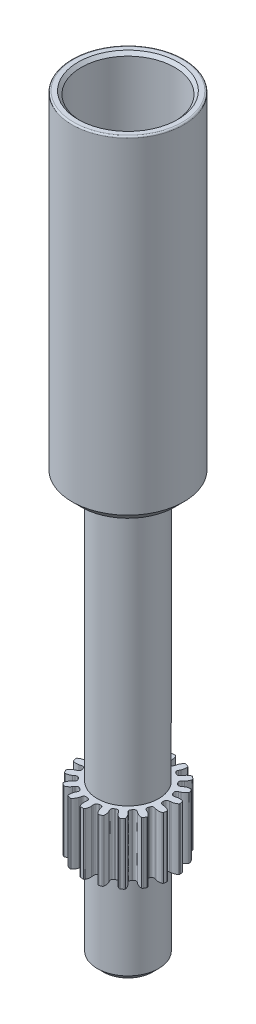
SolidWorks part; units mm, degrees
ref_plane "Front Plane" through (0, 0, 0) normal (0, 0, 1) x (1, 0, 0)
ref_plane "Top Plane" through (0, 0, 0) normal (0, 1, 0) x (1, 0, 0)
ref_plane "Right Plane" through (0, 0, 0) normal (1, 0, 0) x (0, 0, -1)
sketch "Sketch1" plane through (0, 0, 0) normal (0, 0, 1) x (1, 0, 0)
  line L0 (0, 0) -> (-10, 0)
  line L1 (-10, 0) -> (-10, 135)
  line L2 (-10, 135) -> (-18.25, 135)
  line L3 (-18.25, 135) -> (-18.25, 245)
  line L4 (-18.25, 245) -> (-15.25, 245)
  line L5 (-15.25, 245) -> (-15.25, 155)
  line L6 (-15.25, 155) -> (0, 155)
  line L7 (0, 155) -> (0, 0)
  line L8 (-7.3324, 35) -> (8.884, 35) construction
  dimension "D1" = 110
  dimension "D2" = 135
  dimension "D4" = 15.25
  dimension "D5" = 10
  dimension "D6" = 90
  dimension "D7" = 3
revolve "Revolve1" add sketch "Sketch1" angle 360 about L7
chamfer "Chamfer1" distance 3 angle 45 1 edges at (-18.25, 135, 0)
fillet "Fillet1" radius 0.5 1 edges at (-18.25, 245, 0)
ref_axis "Axis1" through (0, 155, 0) along (0, 1, 0)
chamfer "Chamfer2" distance 1 angle 45 1 edges at (-15.25, 245, 0)
ref_plane "Plane1" through (0, 30, 0) normal (0, -1, 0) x (-1, 0, 0)
sketch "Sketch2" plane through (0, 30, 0) normal (0, -1, 0) x (-1, 0, 0)
  line L0 (0, 0) -> (0, 50.5669) construction
  line L1 (0, 0) -> (-2.3642, 54.1494) construction
  line L2 (0, 0) -> (-4.5793, 52.3414) construction
  line L3 (0, 0) -> (-8.4968, 48.1875) construction
  line L16 (-1.133, 12.9505) -> (-1.0023, 11.4562)
  line L17 (-1.997, 11.3253) -> (0, 0)
  line L18 (1.997, 11.3253) -> (0, 0)
  line L19 (1.133, 12.9505) -> (1.0023, 11.4562)
  arc A0 (0.4277, 14.9939) -> (-0.4277, 14.9939) centre (0, 0) ccw
  circle A1 centre (0, 0) radius 13
  arc A2 (0.7715, 14.778) -> (1.133, 12.9505) centre (-2.1947, 13.2417) cw
  circle A3 centre (0, 0) radius 11.5
  arc A6 (-0.7715, 14.778) -> (-1.133, 12.9505) centre (2.1947, 13.2417) ccw
  arc A7 (-1.3073, 14.9429) -> (6.9708, 13.2818) centre (0, 0) ccw
  arc A8 (-0.7715, 14.778) -> (-0.4277, 14.9939) centre (-0.4163, 14.5941) cw
  arc A9 (0.7715, 14.778) -> (0.4277, 14.9939) centre (0.4163, 14.5941) ccw
  point P25 (0, 0)
  point P36 (-0.6543, 14.9857)
  point P39 (0.6543, 14.9857)
  dimension "D1" = 30
  dimension "D2" = 26
  dimension "D3" = 23
  dimension "D5" = 2.5
  dimension "D8" = 0.4
  dimension "D6" = 5
  dimension "D7" = 10
extrude "Boss-Extrude1" add sketch "Sketch2" against normal blind 20 contours A3 L17 L18 | A3 L19 A1 L16 | A0 A6 A1 A2 region at (0, 30, -12.2497) region at (0, 30, -13.9056) region at (0, 30, -7.6278)
fillet "Fillet2" radius 1 2 edges at (1.0023, 40, -11.4562) (-1.0023, 40, -11.4562) curvature continuous yes
pattern_circular "CirPattern2" count 18 over 360 about axis through (0, 155, 0) along (0, 1, 0) of "Fillet2", "Boss-Extrude1"
chamfer "Chamfer3" distance 2 angle 45 1 edges at (-10, 0, 0)
ref_plane "Plane2" through (0, 80, 0) normal (0, 1, 0) x (1, 0, 0)
